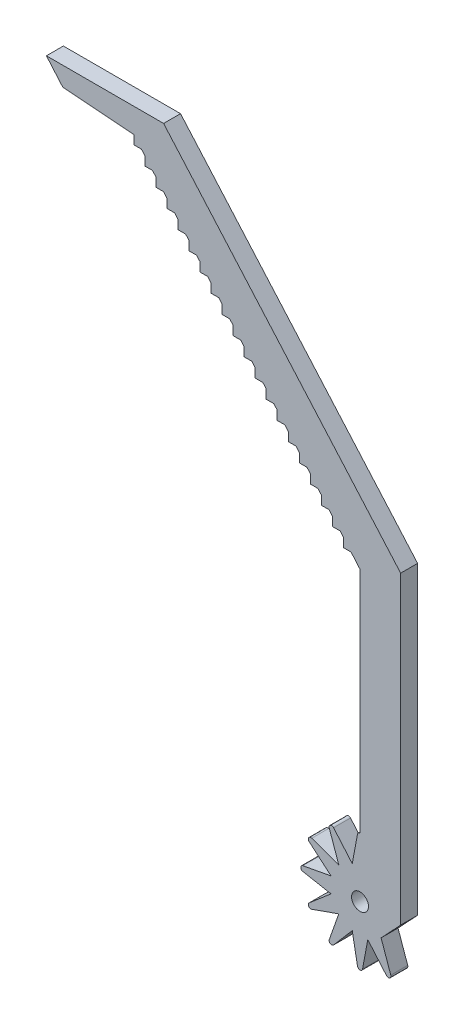
SolidWorks part; units mm, degrees
ref_plane "Front Plane" through (0, 0, 0) normal (0, 0, 1) x (1, 0, 0)
ref_plane "Top Plane" through (0, 0, 0) normal (0, 1, 0) x (1, 0, 0)
ref_plane "Right Plane" through (0, 0, 0) normal (1, 0, 0) x (0, 0, -1)
sketch "Sketch2" plane through (0, 0, 0) normal (0, 0, 1) x (1, 0, 0)
  line L0 (0, 0) -> (0, 17.5)
  line L1 (0, 7.9913) -> (-2.4, 7.9913)
  line L2 (-2.4, 7.9913) -> (-0.7372, 16.8878)
  line L3 (0, 7.9913) -> (2.4, 7.9913)
  line L4 (2.4, 7.9913) -> (0.7372, 16.8878)
  circle A1 centre (0, 0) radius 8.75
  circle A2 centre (0, 0) radius 2.5
  circle A3 centre (0, 0) radius 17.5
  arc A4 (0.7372, 16.8878) -> (-0.7372, 16.8878) centre (0, 16.75) ccw
  dimension "D1" = 5
  dimension "D2" = 17.5
  dimension "D3" = 35
  dimension "D4" = 1.5
  dimension "D5" = 2.4
  dimension "D6" = 2.4
extrude "Boss-Extrude1" add sketch "Sketch2" along normal blind 5 contours A1
extrude "Cut-Extrude1" cut sketch "Sketch2<3>" along normal blind 31 contours A2
sketch "Sketch2<3>" plane through (0, 0, 0) normal (0, 0, 1) x (1, 0, 0) same geometry as "Sketch2"
extrude "Boss-Extrude2" add sketch "Sketch2<4>" along normal blind 5 contours L2 A4 L4 L3 L1
sketch "Sketch2<4>" plane through (0, 0, 0) normal (0, 0, 1) x (1, 0, 0) same geometry as "Sketch2"
pattern_circular "CirPattern2" count 8 every 30 about axis through (0, 0, 5) along (0, 0, -1) of "Boss-Extrude2" reverse direction yes
sketch "Sketch3" plane through (0, 0, 5) normal (0, 0, 1) x (1, 0, 0)
  line L0 (0, 0) -> (0, 85.4895)
  line L1 (0, 85.4895) -> (-37.6578, 145.9046)
  line L2 (-37.6578, 145.9046) -> (-35.2554, 148.3071)
  line L3 (-37.6578, 145.9046) -> (-28.1976, 155.3649)
  line L4 (-28.1976, 155.3649) -> (13.752, 94.4948)
  line L5 (13.752, 94.4948) -> (13.752, 0)
  line L6 (13.752, 0) -> (0, 0)
  line L7 (-37.6578, 145.9046) -> (-52.1367, 157.8484)
  line L8 (-52.1367, 157.8484) -> (-28.1976, 155.3649)
  line L9 (13.752, 0) -> (6.2251, -6.149)
  circle A0 centre (-37.6578, 145.9046) radius 3.3976
sketch "Sketch5" plane through (0, 0, 0) normal (0, 0, 1) x (1, 0, 0)
  line L0 (12, 85) -> (12, 90)
  line L1 (0, 0) -> (12, 0)
  line L2 (0, 0) -> (0, 85)
  line L4 (12, 0) -> (12, 85)
  line L5 (-58, 170) -> (-73, 170)
  line L6 (-66.7906, 162.7699) -> (0, 85)
  line L7 (-58, 170) -> (12, 90)
  line L8 (-73, 170) -> (-92.6, 170)
  line L9 (-92.6, 170) -> (-87.7906, 164.4)
  line L10 (-87.7906, 164.4) -> (-66.7906, 162.7699)
  dimension "D1" = 85
  dimension "D2" = 12
  dimension "D3" = 220.657
  dimension "D4" = 138.814
  dimension "D5" = 85
  dimension "D6" = 15
  dimension "D7" = 90
  dimension "D8" = 5.6
  dimension "D9" = 19.6
  dimension "D10" = 21
  dimension "D11" = 131.186
extrude "Boss-Extrude3" add sketch "Sketch5" along normal blind 5 separate body
sketch "Sketch6" plane through (0, 0, 5) normal (0, 0, 1) x (1, 0, 0)
  line L0 (6.2251, -6.149) -> (12, 0)
  line L1 (12, 0) -> (8.75, 0)
  line L2 (0, 0) -> (12, 0) construction
  line L19 (9.0824, -14.2566) -> (6.2251, -6.149)
  line L20 (2.3166, 8.4378) -> (0.7372, 16.8878)
  line L21 (-0.7372, 16.8878) -> (-2.2937, 8.5602)
  line L22 (-2.2937, 8.5602) -> (-7.8054, 14.9939)
  line L23 (-9.0824, 14.2566) -> (-6.2665, 6.2665)
  line L24 (-6.2665, 6.2665) -> (-14.2566, 9.0824)
  line L25 (-14.9939, 7.8054) -> (-8.5602, 2.2937)
  line L26 (-8.5602, 2.2937) -> (-16.8878, 0.7372)
  line L27 (-16.8878, -0.7372) -> (-8.5602, -2.2937)
  line L28 (-8.5602, -2.2937) -> (-14.9939, -7.8054)
  line L29 (-14.2566, -9.0824) -> (-6.2665, -6.2665)
  line L30 (-6.2665, -6.2665) -> (-9.0824, -14.2566)
  line L31 (-7.8054, -14.9939) -> (-2.2937, -8.5602)
  line L32 (-2.2937, -8.5602) -> (-0.7372, -16.8878)
  line L33 (0.7372, -16.8878) -> (2.2937, -8.5602)
  line L34 (2.2937, -8.5602) -> (7.8054, -14.9939)
  arc A0 (6.2251, -6.149) -> (2.3166, 8.4378) centre (0, 0) ccw construction
  arc A10 (6.2251, -6.149) -> (2.3166, 8.4378) centre (0, 0) ccw
  arc A11 (0.7372, 16.8878) -> (-0.7372, 16.8878) centre (0, 16.75) ccw
  arc A12 (-7.8054, 14.9939) -> (-9.0824, 14.2566) centre (-8.375, 14.5059) ccw
  arc A13 (-14.2566, 9.0824) -> (-14.9939, 7.8054) centre (-14.5059, 8.375) ccw
  arc A14 (-16.8878, 0.7372) -> (-16.8878, -0.7372) centre (-16.75, 0) ccw
  arc A15 (-14.9939, -7.8054) -> (-14.2566, -9.0824) centre (-14.5059, -8.375) ccw
  arc A16 (-9.0824, -14.2566) -> (-7.8054, -14.9939) centre (-8.375, -14.5059) ccw
  arc A17 (-0.7372, -16.8878) -> (0.7372, -16.8878) centre (0, -16.75) ccw
  arc A18 (7.8054, -14.9939) -> (9.0824, -14.2566) centre (8.375, -14.5059) ccw
  arc A19 (6.2251, -6.149) -> (8.75, 0) centre (0, 0) ccw
  arc M27 (6.2251, -6.149) -> (2.3166, 8.4378) centre (0, 0) ccw
  dimension "D1" = 0
extrude "Boss-Extrude4" add sketch "Sketch6" against normal blind 5 contours L0 L1 M27 region at (9.514, -1.5838, 5)
sketch "Sketch7" plane through (0, 0, 5) normal (0, 0, 1) x (1, 0, 0)
  circle A0 centre (0, 0) radius 2.5
extrude "Cut-Extrude2" cut sketch "Sketch7" against normal blind 5
sketch "Sketch8" plane through (0, 0, 5) normal (0, 0, 1) x (1, 0, 0)
  line L0 (-66.7906, 162.7699) -> (-66.7906, 160.1327)
  line L1 (-66.7906, 160.1327) -> (-64.5257, 160.1327)
  line L2 (-66.7906, 162.7699) -> (0, 85) construction
  line L3 (-64.5257, 160.1327) -> (-66.7906, 162.7699)
extrude "Boss-Extrude5" add sketch "Sketch8" against normal blind 5
pattern_linear "LPattern1" count 20 spacing 5 along (0.6515, -0.7586, 0) of "Boss-Extrude5"
